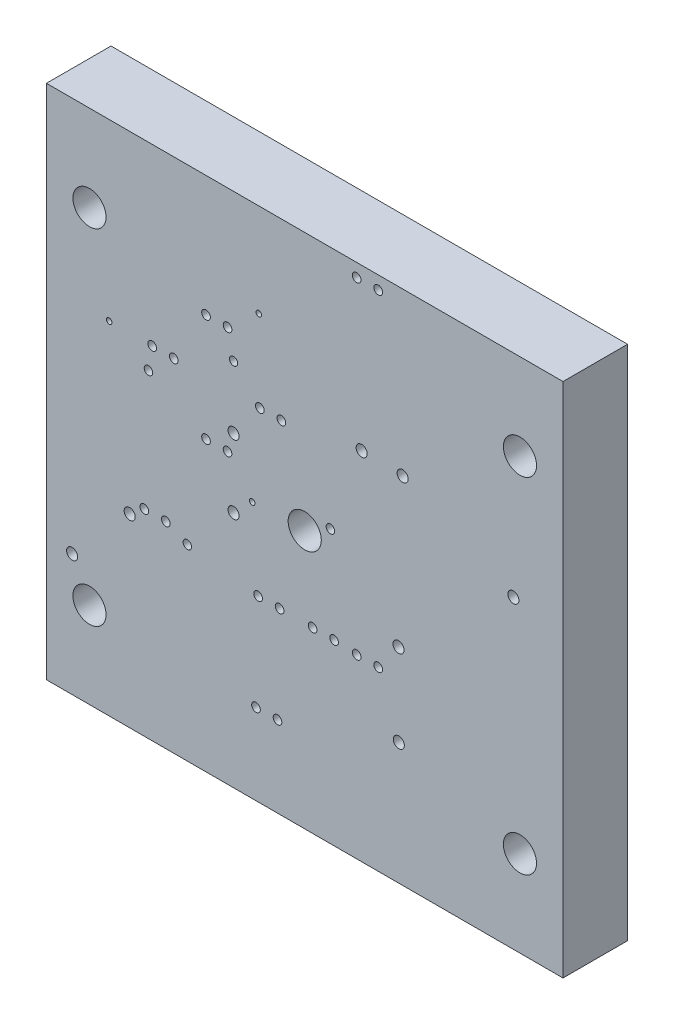
SolidWorks part; units mm, degrees
ref_plane "Front Plane" through (0, 0, 0) normal (0, 0, 1) x (1, 0, 0)
ref_plane "Top Plane" through (0, 0, 0) normal (0, 1, 0) x (1, 0, 0)
ref_plane "Right Plane" through (0, 0, 0) normal (1, 0, 0) x (0, 0, -1)
sketch "Sketch1" plane through (0, 0, 0) normal (0, 0, 1) x (1, 0, 0)
  line L1 (-152.4, 152.4) -> (152.4, 152.4)
  line L2 (-152.4, 152.4) -> (-152.4, -152.4)
  line L3 (-152.4, -152.4) -> (152.4, -152.4)
  line L4 (152.4, 152.4) -> (152.4, -152.4)
  line L5 (-152.4, 152.4) -> (152.4, -152.4) construction
  line L6 (-152.4, -152.4) -> (152.4, 152.4) construction
  point P0 (0, 0)
  dimension "D1" = 304.8
  dimension "D2" = 304.8
extrude "Boss-Extrude1" add sketch "Sketch1" along normal blind 38.1
sketch "Sketch2" plane through (0, 0, 38.1) normal (0, 0, 1) x (1, 0, 0)
  line L0 (-152.4, 0) -> (152.4, 0) construction
  line L5 (-152.4, 152.4) -> (-152.4, -152.4) construction
  line L6 (152.4, -152.4) -> (152.4, 152.4) construction
  line L7 (-152.4, -101.6) -> (152.4, -101.6) construction
  line L8 (-152.4, 101.6) -> (152.4, 101.6) construction
  line L9 (0, 101.6) -> (0, -101.6) construction
  line L10 (127, 101.6) -> (127, -101.6) construction
  line L11 (-127, 101.6) -> (-127, -101.6) construction
  circle A0 centre (-127, 101.6) radius 6.5151
  circle A1 centre (127, 101.6) radius 6.5151
  circle A2 centre (127, -101.6) radius 6.5151
  circle A3 centre (-127, -101.6) radius 6.5151
  circle A4 centre (0, 0) radius 6.5151
  dimension "D5" = 13.0302
  dimension "D1" = 101.6
  dimension "D2" = 101.6
  dimension "D3" = 127
  dimension "D4" = 127
extrude "HAAS T-Slot Holes" cut sketch "Sketch2" against normal through all
sketch "Sketch3" plane through (0, 0, 38.1) normal (0, 0, 1) x (1, 0, 0)
  circle A0 centre (-127, 101.6) radius 9.779
  circle A1 centre (127, 101.6) radius 9.779
  circle A2 centre (0, 0) radius 9.779
  circle A3 centre (127, -101.6) radius 9.779
  circle A4 centre (-127, -101.6) radius 9.779
  dimension "D1" = 19.558
extrude "HAAS Counter Bores" cut sketch "Sketch3" against normal offset from surface (22.225 mm away) 15.875 contours A0 | A1 | A2 | A3 | A4 up to face at (6.5151, 0, 0)
sketch "Sketch4" plane through (0, 0, 38.1) normal (0, 0, 1) x (1, 0, 0)
  circle A1 centre (55.3386, -31.7863) radius 3.2639
  circle A2 centre (55.3386, -31.7863) radius 3.2639
  circle A5 centre (-103.2689, -43.0628) radius 3.2639
  circle A6 centre (-103.2689, -43.0628) radius 3.2639
  circle A7 centre (-41.9849, -11.8461) radius 3.2639
  circle A8 centre (-41.9849, -11.8461) radius 3.2639
  circle A9 centre (-41.9849, 28.7939) radius 3.2639
  circle A10 centre (-41.9849, 28.7939) radius 3.2639
  circle A11 centre (123.1151, 27.5239) radius 3.2639
  circle A12 centre (123.1151, 27.5239) radius 3.2639
  circle A16 centre (-137.2349, -80.4261) radius 3.2639
  circle A17 centre (55.5146, -80.4261) radius 3.2639
  circle A18 centre (33.6023, 57.6321) radius 3.2639
  circle A19 centre (57.7861, 56.7971) radius 3.2639
  dimension "D1" = 0
  dimension "D3" = 0
  dimension "D4" = 0
  dimension "D5" = 0
  dimension "D6" = 0
extrude "Cut-Extrude1" cut sketch "Sketch4" against normal blind 19.05
sketch "Sketch5" plane through (0, 0, 38.1) normal (0, 0, 1) x (1, 0, 0)
  circle A0 centre (-41.9849, 65.6239) radius 2.4146
  circle A1 centre (-92.2093, 35.7436) radius 2.5
  circle A2 centre (-69.2545, -41.7505) radius 2.5
  circle A3 centre (15.1651, 8.4739) radius 2.5
extrude "Cut-Extrude2" cut sketch "Sketch5" against normal blind 12.7
sketch "Sketch6" plane through (0, 0, 38.1) normal (0, 0, 1) x (1, 0, 0)
  circle A1 centre (17.3582, -47.1908) radius 2.5527
  circle A2 centre (17.3582, -47.1908) radius 2.5527
  circle A3 centre (-45.5295, 17.658) radius 2.5527
  circle A4 centre (-45.5295, 17.658) radius 2.5527
  circle A5 centre (-81.9518, -36.2493) radius 2.5527
  circle A6 centre (-81.9518, -36.2493) radius 2.5527
  circle A7 centre (43.3705, -48.0915) radius 2.5527
  circle A8 centre (43.3705, -48.0915) radius 2.5527
  circle A9 centre (-16.0578, -104.6462) radius 2.5527
  circle A10 centre (-16.0578, -104.6462) radius 2.5527
  circle A11 centre (-13.7795, 49.408) radius 2.5527
  circle A12 centre (-13.7795, 49.408) radius 2.5527
  circle A13 centre (-14.8141, -47.1908) radius 2.5527
  circle A14 centre (-14.8141, -47.1908) radius 2.5527
  circle A17 centre (43.3705, 144.658) radius 2.5527
  circle A18 centre (43.3705, 144.658) radius 2.5527
  circle A19 centre (-45.5295, 81.158) radius 2.5527
  circle A20 centre (-45.5295, 81.158) radius 2.5527
  circle A21 centre (-77.2795, 49.408) radius 2.5527
  circle A22 centre (-77.2795, 49.408) radius 2.5527
  circle A27 centre (-28.7578, -104.6462) radius 2.5527
  circle A28 centre (-28.7578, -104.6462) radius 2.5527
  circle A29 centre (4.6582, -47.1908) radius 2.5527
  circle A30 centre (4.6582, -47.1908) radius 2.5527
  circle A31 centre (-58.2295, 17.658) radius 2.5527
  circle A32 centre (-58.2295, 17.658) radius 2.5527
  circle A33 centre (-94.6518, -36.2493) radius 2.5527
  circle A34 centre (-94.6518, -36.2493) radius 2.5527
  circle A35 centre (30.6705, -48.0915) radius 2.5527
  circle A36 centre (30.6705, -48.0915) radius 2.5527
  circle A37 centre (-89.9795, 49.408) radius 2.5527
  circle A38 centre (-89.9795, 49.408) radius 2.5527
  circle A39 centre (-58.2295, 81.158) radius 2.5527
  circle A40 centre (-58.2295, 81.158) radius 2.5527
  circle A41 centre (-26.4795, 49.408) radius 2.5527
  circle A42 centre (-26.4795, 49.408) radius 2.5527
  circle A43 centre (-27.5141, -47.1908) radius 2.5527
  circle A44 centre (-27.5141, -47.1908) radius 2.5527
  circle A45 centre (-115.3795, 49.408) radius 1.6319
  circle A46 centre (-115.3795, 49.408) radius 1.6319
  circle A47 centre (30.6705, 144.658) radius 2.5527
  circle A48 centre (30.6705, 144.658) radius 2.5527
  circle A49 centre (-30.9599, -0.8164) radius 1.6319
  circle A50 centre (-30.9599, -0.8164) radius 1.6319
  circle A51 centre (-27.1034, 97.338) radius 1.6319
  circle A52 centre (-27.1034, 97.338) radius 1.6319
  point P0 (0, 0)
  dimension "D1" = 0
  dimension "D2" = 0
  dimension "D3" = 0
  dimension "D4" = 0
  dimension "D5" = 0
  dimension "D6" = 0
  dimension "D7" = 0
  dimension "D9" = 0
  dimension "D10" = 0
  dimension "D11" = 0
  dimension "D14" = 0
  dimension "D15" = 0
  dimension "D16" = 0
  dimension "D17" = 0
  dimension "D18" = 0
  dimension "D19" = 0
  dimension "D20" = 0
  dimension "D21" = 0
  dimension "D22" = 0
  dimension "D23" = 0
  dimension "D24" = 0
  dimension "D25" = 0
  dimension "D26" = 0
extrude "Cut-Extrude3" cut sketch "Sketch6" against normal blind 19.05
